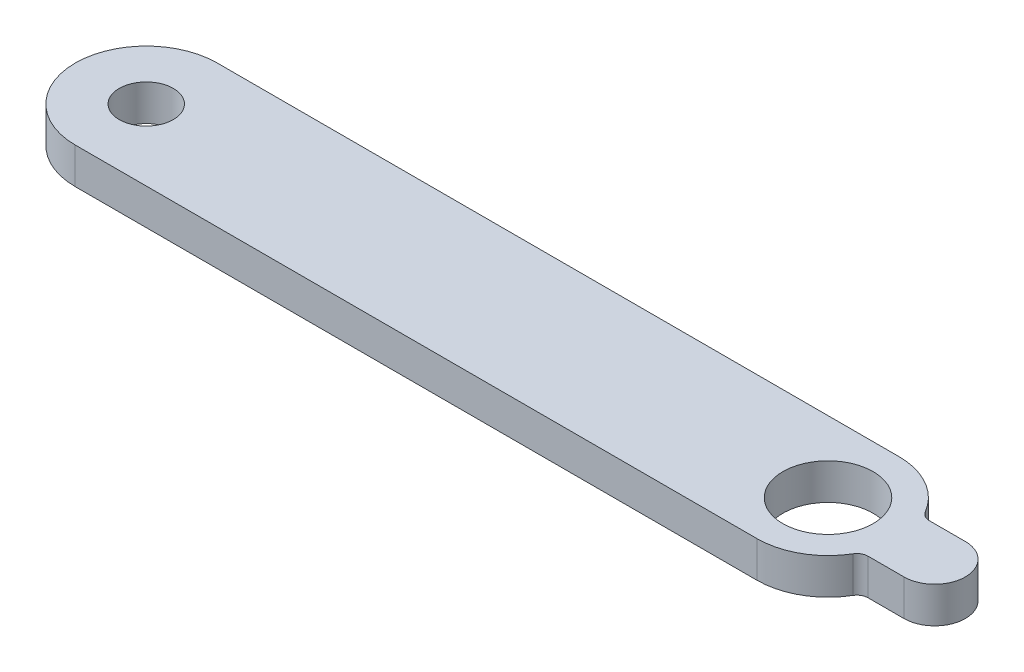
SolidWorks part; units mm, degrees
ref_plane "Front Plane" through (0, 0, 0) normal (0, 0, 1) x (1, 0, 0)
ref_plane "Top Plane" through (0, 0, 0) normal (0, 1, 0) x (1, 0, 0)
ref_plane "Right Plane" through (0, 0, 0) normal (1, 0, 0) x (0, 0, -1)
sketch "Sketch1" plane through (0, 0, 0) normal (0, 1, 0) x (1, 0, 0)
  line L0 (-30.066, 0.0378) -> (29.934, 0.0378) construction
  line L1 (-30.066, 6.2878) -> (29.934, 6.2878)
  line L2 (-30.066, -6.2122) -> (29.934, -6.2122)
  line L4 (36.1688, 2.7378) -> (39.3233, 2.7378)
  line L6 (36.1688, -2.6622) -> (39.3233, -2.6622)
  arc A0 (-30.066, 6.2878) -> (-30.066, -6.2122) centre (-30.066, 0.0378) ccw
  arc A1 (29.934, -6.2122) -> (35.3088, -3.1519) centre (29.934, 0.0378) ccw
  circle A2 centre (-30.066, 0.0378) radius 2.38
  arc A4 (35.3088, 3.2275) -> (29.934, 6.2878) centre (29.934, 0.0378) ccw
  arc A5 (39.3233, -2.6622) -> (39.3233, 2.7378) centre (39.3233, 0.0378) ccw
  arc A6 (35.3088, -3.1519) -> (36.1688, -2.6622) centre (36.1688, -3.6622) cw
  arc A7 (36.1688, 2.7378) -> (35.3088, 3.2275) centre (36.1688, 3.7378) cw
  circle A8 centre (29.934, 0.0378) radius 3.97
  point P2 (0, 0)
  point P19 (35.5707, -2.6622)
  point P22 (35.5707, 2.7378)
  dimension "D3" = 4.76
  dimension "D4" = 1
  dimension "D6" = 6.25
  dimension "D7" = 6.25
  dimension "D8" = 7.94
  dimension "D1" = 12.5
  dimension "D2" = 60
  dimension "D5" = 5.4
extrude "Boss-Extrude1" add sketch "Sketch1" along normal blind 3.175
